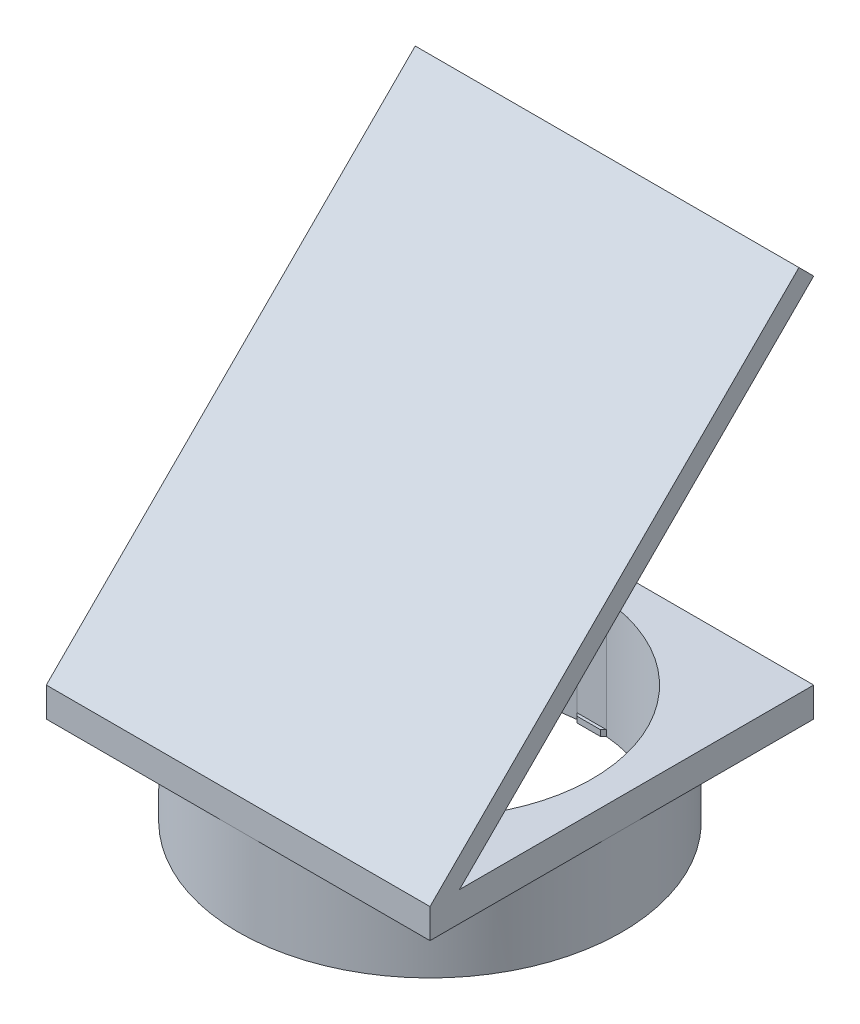
SolidWorks part; units mm, degrees
ref_plane "Front Plane" through (0, 0, 0) normal (0, 0, 1) x (1, 0, 0)
ref_plane "Top Plane" through (0, 0, 0) normal (0, 1, 0) x (1, 0, 0)
ref_plane "Right Plane" through (0, 0, 0) normal (1, 0, 0) x (0, 0, -1)
sketch "Sketch1" plane through (0, 0, 0) normal (0, 1, 0) x (1, 0, 0)
  line L0 (-1, 10.9545) -> (1, 10.9545)
  line L1 (10.9545, 1) -> (10.9545, -1)
  line L2 (1, -10.9545) -> (-1, -10.9545)
  line L3 (-10.9545, -1) -> (-10.9545, 1)
  arc A0 (-1, 10.9545) -> (-10.9545, 1) centre (0, 0) ccw
  circle A1 centre (0, 0) radius 13
  arc A2 (10.9545, 1) -> (1, 10.9545) centre (0, 0) ccw
  arc A3 (1, -10.9545) -> (10.9545, -1) centre (0, 0) ccw
  arc A4 (-10.9545, -1) -> (-1, -10.9545) centre (0, 0) ccw
  point P15 (0, 0)
  dimension "D1" = 22
  dimension "D2" = 2
  dimension "D3" = 1
  dimension "D4" = 4
extrude "Boss-Extrude1" add sketch "Sketch1" along normal blind 6
sketch "Sketch2" plane through (0, 0, -10.9545) normal (0, 0, 1) x (1, 0, 0)
  line L0 (1, 6) -> (1, 0) construction
  line L1 (-1, 0) -> (1, 0)
  line L2 (-1, 0) -> (-1, 0.4)
  line L3 (-1, 0.4) -> (1, 0.4)
  line L4 (1, 0) -> (1, 0.4)
  dimension "D1" = 0.4
extrude "Boss-Extrude2" add sketch "Sketch2" along normal blind 0.2
sketch "Sketch3" plane through (-10.9545, 0, 0) normal (1, 0, 0) x (0, 0, -1)
  line L0 (1, 6) -> (1, 0) construction
  line L1 (-1, 0) -> (1, 0)
  line L2 (-1, 0) -> (-1, 0.4)
  line L3 (-1, 0.4) -> (1, 0.4)
  line L4 (1, 0) -> (1, 0.4)
  dimension "D1" = 0.4
extrude "Boss-Extrude3" add sketch "Sketch3" along normal blind 0.2
sketch "Sketch4" plane through (0, 0, 10.9545) normal (0, 0, -1) x (-1, 0, 0)
  line L0 (1, 6) -> (1, 0) construction
  line L1 (-1, 0) -> (1, 0)
  line L2 (-1, 0) -> (-1, 0.4)
  line L3 (-1, 0.4) -> (1, 0.4)
  line L4 (1, 0) -> (1, 0.4)
  dimension "D1" = 0.4
extrude "Boss-Extrude4" add sketch "Sketch4" along normal blind 0.2
chamfer "Chamfer1" distance 0.2 angle 45 6 edges at (1, 0.2, -10.7545) (-1, 0.2, -10.7545) (-10.7545, 0.2, 1) (-10.7545, 0.2, -1) (-1, 0.2, 10.7545) (1, 0.2, 10.7545)
sketch "Sketch5" plane through (10.9545, 0, 0) normal (-1, 0, 0) x (0, 0, 1)
  line L0 (1, 6) -> (1, 0) construction
  line L1 (-1, 0) -> (1, 0)
  line L2 (-1, 0) -> (-1, 0.4)
  line L3 (-1, 0.4) -> (1, 0.4)
  line L4 (1, 0) -> (1, 0.4)
  dimension "D1" = 0.4
extrude "Boss-Extrude5" add sketch "Sketch5" along normal blind 0.2
chamfer "Chamfer2" distance 0.2 angle 45 2 edges at (10.7545, 0.2, 1) (10.7545, 0.2, -1)
sketch "Sketch6" plane through (0, 6, 0) normal (0, 1, 0) x (1, 0, 0)
  line L1 (13, -13) -> (-13, -13)
  line L2 (13, -13) -> (13, 13)
  line L3 (13, 13) -> (-13, 13)
  line L4 (-13, -13) -> (-13, 13)
  line L5 (13, -13) -> (-13, 13) construction
  line L6 (13, 13) -> (-13, -13) construction
  point P0 (0, 0)
  dimension "D1" = 26
  dimension "D2" = 26
extrude "Boss-Extrude6" add sketch "Sketch6" along normal blind 2
sketch "Sketch7" plane through (0, 6, 0) normal (0, -1, 0) x (1, 0, 0)
  circle A0 centre (0, 0) radius 11
extrude "Cut-Extrude1" cut sketch "Sketch7" against normal blind 2
sketch "Sketch8" plane through (13, 0, 0) normal (1, 0, 0) x (0, 0, -1)
  line L0 (-13, 8) -> (12.0002, 33.0002)
  line L1 (12.0002, 33.0002) -> (13, 32.0003)
  line L2 (13, 32.0003) -> (-11.0003, 8)
  line L3 (-13, 8) -> (13, 8) construction
  line L4 (-11.0003, 8) -> (-13, 8)
  dimension "D1" = 1.414
  dimension "D2" = 45
  dimension "D3" = 0
extrude "Boss-Extrude7" add sketch "Sketch8" against normal blind 26
